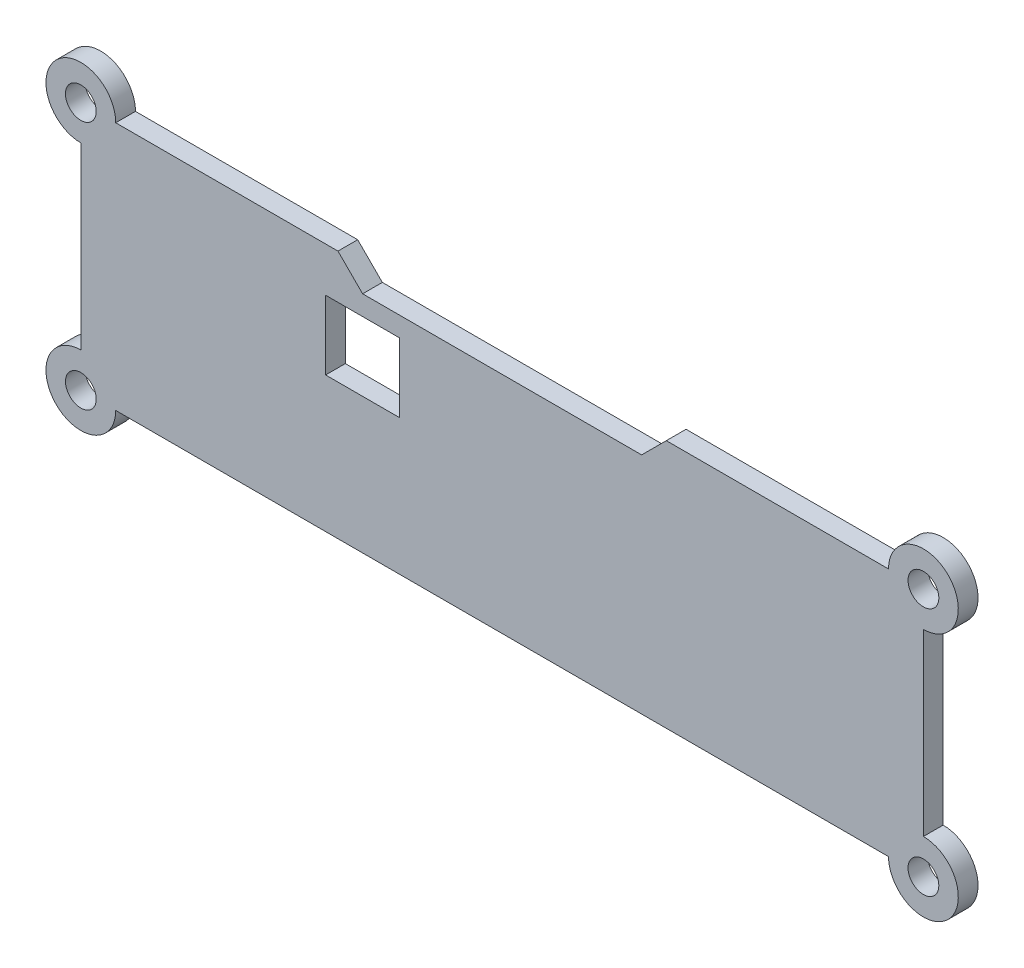
SolidWorks part; units mm, degrees
ref_plane "Front Plane" through (0, 0, 0) normal (0, 0, 1) x (1, 0, 0)
ref_plane "Top Plane" through (0, 0, 0) normal (0, 1, 0) x (1, 0, 0)
ref_plane "Right Plane" through (0, 0, 0) normal (1, 0, 0) x (0, 0, -1)
sketch "Sketch1" plane through (0, 0, 0) normal (0, 0, 1) x (1, 0, 0)
  line L0 (-16.6405, -31.6383) -> (-34.1383, -14.1405)
  line L2 (-34.1383, -14.1405) -> (-34.1383, 14.1405)
  line L4 (-34.1383, 14.1405) -> (-14.1405, 34.1383)
  line L6 (-14.1405, 34.1383) -> (14.1405, 34.1383)
  line L8 (14.1405, 34.1383) -> (34.1383, 14.1405)
  line L10 (34.1383, 14.1405) -> (34.1383, -14.1405)
  line L12 (34.1383, -14.1405) -> (16.6405, -31.6383)
  line L14 (16.6405, -31.6383) -> (39.1645, -31.6383)
  line L15 (16.6405, -31.6383) -> (39.1645, -31.6383)
  line L16 (42.7, -35.1738) -> (42.7, -53.3527)
  line L17 (42.7, -35.1738) -> (42.7, -53.3527)
  line L18 (39.1645, -56.8883) -> (-39.1645, -56.8883)
  line L19 (39.1645, -56.8883) -> (-39.1645, -56.8883)
  line L20 (-42.7, -53.3527) -> (-42.7, -35.1738)
  line L21 (-42.7, -53.3527) -> (-42.7, -35.1738)
  line L22 (-39.1645, -31.6383) -> (-16.6405, -31.6383)
  line L23 (-39.1645, -31.6383) -> (-16.6405, -31.6383)
  line L24 (-16.6405, -31.6383) -> (-14.1405, -34.1383)
  line L25 (-14.1405, -34.1383) -> (14.1405, -34.1383)
  line L26 (14.1405, -34.1383) -> (16.6405, -31.6383)
  line L27 (0, -56.8883) -> (0, -34.1383) construction
  line L28 (-0.525, -56.8883) -> (0.525, -56.8883) construction
  line L29 (-42.7, -44.2633) -> (42.7, -44.2633) construction
  arc A0 (42.7, -35.1738) -> (39.1645, -31.6383) centre (42.7, -31.6383) ccw
  arc A1 (42.7, -35.1738) -> (39.1645, -31.6383) centre (42.7, -31.6383) ccw
  arc A2 (39.1645, -56.8883) -> (42.7, -53.3527) centre (42.7, -56.8883) ccw
  arc A3 (39.1645, -56.8883) -> (42.7, -53.3527) centre (42.7, -56.8883) ccw
  arc A4 (-42.7, -53.3527) -> (-39.1645, -56.8883) centre (-42.7, -56.8883) ccw
  arc A5 (-42.7, -53.3527) -> (-39.1645, -56.8883) centre (-42.7, -56.8883) ccw
  arc A6 (-39.1645, -31.6383) -> (-42.7, -35.1738) centre (-42.7, -31.6383) ccw
  arc A7 (-39.1645, -31.6383) -> (-42.7, -35.1738) centre (-42.7, -31.6383) ccw
  circle A8 centre (-42.7, -31.6383) radius 1.56
  circle A9 centre (-42.7, -56.8883) radius 1.56
  circle A10 centre (42.7, -56.8883) radius 1.56
  circle A11 centre (42.7, -31.6383) radius 1.56
  dimension "D1" = 3.12
extrude "Boss-Extrude1" add sketch "Sketch1" along normal blind 2
sketch "Sketch2" plane through (0, 0, 2) normal (0, 0, 1) x (1, 0, 0)
  line L0 (14.1405, -34.1383) -> (-14.1405, -34.1383) construction
  line L1 (-17.8905, -36.1383) -> (-10.3905, -36.1383)
  line L2 (-17.8905, -36.1383) -> (-17.8905, -43.1383)
  line L3 (-17.8905, -43.1383) -> (-10.3905, -43.1383)
  line L4 (-10.3905, -36.1383) -> (-10.3905, -43.1383)
  line L5 (-14.1405, -43.1383) -> (-14.1405, -36.1383) construction
  line L6 (-17.8905, -39.6383) -> (-10.3905, -39.6383) construction
  point P0 (-14.1405, -39.6383)
  dimension "D1" = 7.5
  dimension "D2" = 2
  dimension "D3" = 7
extrude "Cut-Extrude1" cut sketch "Sketch2" against normal up to next
